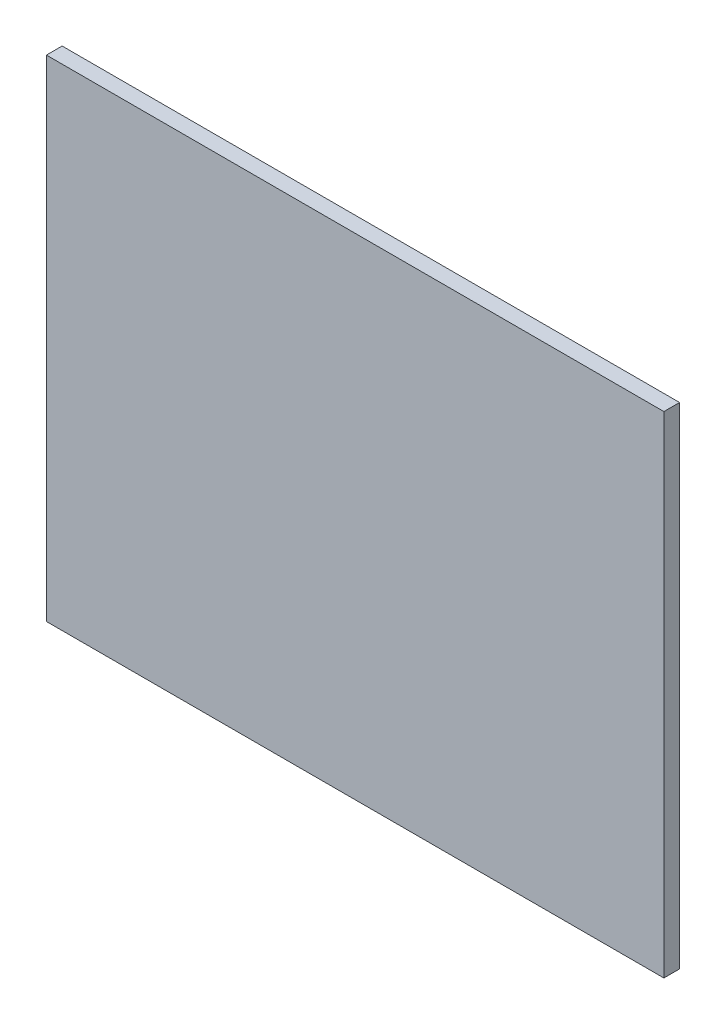
SolidWorks part; units mm, degrees
ref_plane "Alzado" through (0, 0, 0) normal (0, 0, 1) x (1, 0, 0)
ref_plane "Planta" through (0, 0, 0) normal (0, 1, 0) x (1, 0, 0)
ref_plane "Vista lateral" through (0, 0, 0) normal (1, 0, 0) x (0, 0, -1)
sketch "Croquis1" plane through (0, 0, 0) normal (0, 0, 1) x (1, 0, 0)
  line L0 (0, 215.0467) -> (0, -209.8802) construction
  line L1 (-236, -187.5) -> (236, -187.5)
  line L2 (-236, -187.5) -> (-236, 187.5)
  line L3 (-236, 187.5) -> (236, 187.5)
  line L4 (236, -187.5) -> (236, 187.5)
  line L5 (-236, -187.5) -> (236, 187.5) construction
  line L6 (-236, 187.5) -> (236, -187.5) construction
  line L7 (-264.2115, 0) -> (260.4911, 0) construction
  point P0 (0, 0)
  dimension "D1" = 375
  dimension "D2" = 472
extrude "Saliente-Extruir1" add sketch "Croquis1" along normal mid plane 12
sketch "Croquis2" plane through (0, 0, 0) normal (0, 0, 1) x (1, 0, 0)
  line L0 (-236, 187.5) -> (-236, -187.5) construction
  line L6 (0, 203.0536) -> (0, -187.5) construction
  line L7 (-236, -187.5) -> (236, -187.5) construction
  line L8 (-230, 0) -> (230, 0) construction
  line L9 (-230, 181.5) -> (-230, -187.5)
  line L10 (230, -187.5) -> (230, 181.5)
  line L11 (230, 181.5) -> (-230, 181.5)
  line L12 (-230, 181.5) -> (-230, -187.5) construction
  line L13 (230, -187.5) -> (230, 181.5) construction
  line L14 (230, 181.5) -> (-230, 181.5) construction
  line L16 (-230, 181.5) -> (-176.65, 181.5) construction
  line L17 (-230, 181.5) -> (-230, 140) construction
  circle A0 centre (-176.65, 181.5) radius 3
  circle A1 centre (-230, 70) radius 3
  circle A2 centre (-230, 140) radius 3
  circle A3 centre (-106.65, 181.5) radius 3
  circle A4 centre (-36.65, 181.5) radius 3
  circle A5 centre (36.65, 181.5) radius 3
  circle A6 centre (106.65, 181.5) radius 3
  circle A7 centre (-230, -140) radius 3
  circle A8 centre (-230, -70) radius 3
  circle A9 centre (230, -140) radius 3
  circle A10 centre (230, -70) radius 3
  circle A11 centre (230, 70) radius 3
  circle A12 centre (230, 140) radius 3
  circle A13 centre (176.65, 181.5) radius 3
  dimension "D2" = 59.35
  dimension "D3" = 3
  dimension "D1" = 6
extrude "Cortar-Extruir1" cut sketch "Croquis2" against normal blind 12
